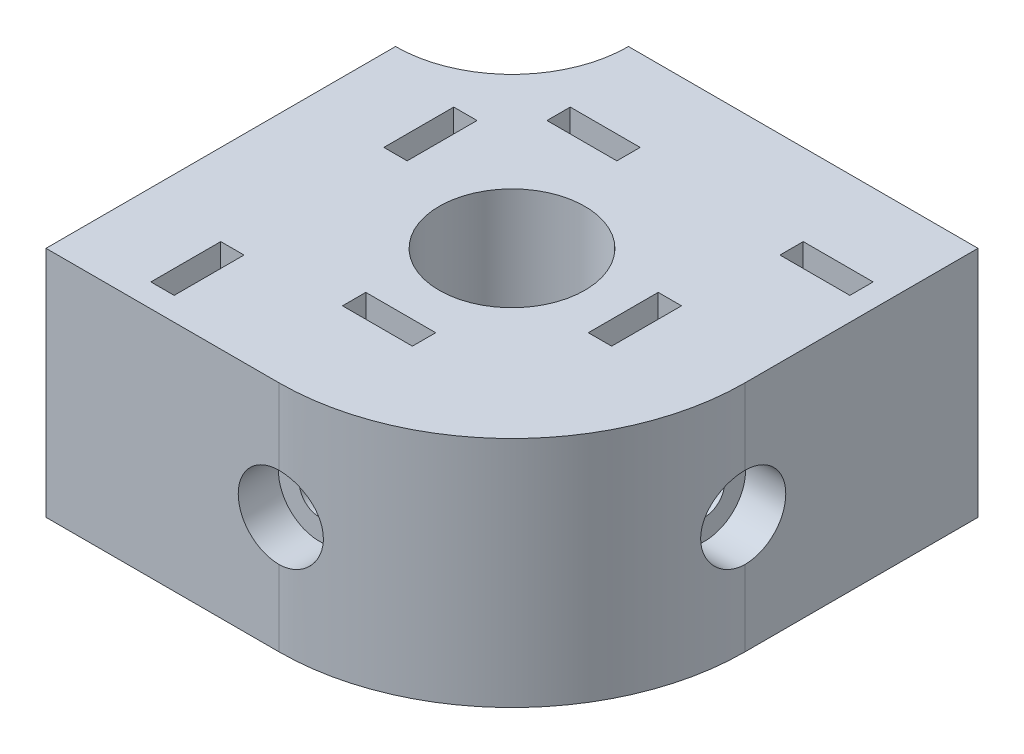
SolidWorks part; units mm, degrees
ref_plane "Front Plane" through (0, 0, 0) normal (0, 0, 1) x (1, 0, 0)
ref_plane "Top Plane" through (0, 0, 0) normal (0, 1, 0) x (1, 0, 0)
ref_plane "Right Plane" through (0, 0, 0) normal (1, 0, 0) x (0, 0, -1)
sketch "Sketch1" plane through (0, 0, 0) normal (0, 1, 0) x (1, 0, 0)
  line L1 (-20, -20) -> (20, -20)
  line L2 (-20, -20) -> (-20, 20)
  line L3 (-20, 20) -> (20, 20)
  line L4 (20, -20) -> (20, 20)
  line L5 (-20, -20) -> (20, 20) construction
  line L6 (-20, 20) -> (20, -20) construction
  circle A0 centre (0, 0) radius 6.25
  point P0 (0, 0)
  dimension "D2" = 12.5
  dimension "D1" = 40
extrude "Boss-Extrude1" add sketch "Sketch1" along normal blind 20
sketch "Sketch2" plane through (-20, 0, 0) normal (-1, 0, 0) x (0, 0, 1)
  line L0 (-5, 15) -> (0, 5) construction
  line L1 (0, 5) -> (15, 15) construction
  line L2 (15, 15) -> (-5, 15) construction
  line L3 (-20, 20) -> (20, 20) construction
  line L4 (-20, 0) -> (20, 0) construction
  line L5 (20, 20) -> (20, 0) construction
  line L6 (-20, 20) -> (-20, 0) construction
  line L7 (0, -11) -> (0, 11) construction
  circle A0 centre (-5, 15) radius 1.7
  circle A1 centre (15, 15) radius 1.7
  circle A2 centre (0, 5) radius 1.7
  dimension "D5" = 3.4
  dimension "D1" = 5
  dimension "D2" = 5
  dimension "D3" = 5
  dimension "D4" = 15
extrude "Cut-Extrude1" cut sketch "Sketch2" against normal blind 11
sketch "Sketch3" plane through (-20, 0, 0) normal (-1, 0, 0) x (0, 0, 1)
  line L1 (-8, 12) -> (-2, 12)
  line L2 (-8, 12) -> (-8, 18)
  line L3 (-8, 18) -> (-2, 18) construction
  line L4 (-2, 12) -> (-2, 18)
  line L5 (-8, 12) -> (-2, 18) construction
  line L6 (-8, 18) -> (-2, 12) construction
  line L7 (12, 12) -> (18, 12)
  line L8 (12, 12) -> (12, 18)
  line L9 (12, 18) -> (18, 18) construction
  line L10 (18, 12) -> (18, 18)
  line L11 (12, 12) -> (18, 18) construction
  line L12 (12, 18) -> (18, 12) construction
  line L13 (-3, 8) -> (3, 8)
  line L14 (-3, 8) -> (-3, 2)
  line L15 (-3, 2) -> (3, 2) construction
  line L16 (3, 8) -> (3, 2)
  line L17 (-3, 8) -> (3, 2) construction
  line L18 (-3, 2) -> (3, 8) construction
  line L20 (-8, 18) -> (-8, 20)
  line L21 (-20, 20) -> (20, 20) construction
  line L22 (-8, 20) -> (-2, 20)
  line L23 (-2, 20) -> (-2, 18)
  line L24 (12, 18) -> (12, 20)
  line L25 (12, 20) -> (18, 20)
  line L26 (18, 20) -> (18, 18)
  line L27 (-3, 2) -> (-3, 0)
  line L28 (-20, 0) -> (20, 0) construction
  line L29 (-3, 0) -> (3, 0)
  line L30 (3, 0) -> (3, 2)
  point P0 (-5, 15)
  point P6 (15, 15)
  point P12 (0, 5)
  dimension "D1" = 6
  dimension "D2" = 6
extrude "Cut-Extrude2" cut sketch "Sketch3" against normal blind 2 from offset 7 offset against normal yes
sketch "Sketch4" plane through (0, 0, 20) normal (0, 0, 1) x (1, 0, 0)
  line L0 (0, 0) -> (0, 20) construction
  line L1 (-20, 20) -> (20, 20) construction
  circle A0 centre (0, 10) radius 1.7
  dimension "D1" = 3.4
extrude "Cut-Extrude3" cut sketch "Sketch4" against normal up to next
sketch "Sketch5" plane through (0, 0, 20) normal (0, 0, 1) x (1, 0, 0)
  line L0 (-3, 13) -> (-3, 20)
  line L1 (-3, 7) -> (3, 7)
  line L2 (-3, 7) -> (-3, 13)
  line L3 (-3, 13) -> (3, 13) construction
  line L4 (3, 7) -> (3, 13)
  line L5 (-3, 7) -> (3, 13) construction
  line L6 (-3, 13) -> (3, 7) construction
  line L7 (-20, 20) -> (20, 20) construction
  line L8 (-3, 20) -> (3, 20)
  line L9 (3, 20) -> (3, 13)
  point P0 (0, 10)
  dimension "D1" = 6
extrude "Cut-Extrude4" cut sketch "Sketch5" against normal blind 2 from offset 8.45 offset against normal yes
sketch "Sketch6" plane through (0, 0, 20) normal (0, 0, 1) x (1, 0, 0)
  circle A0 centre (0, 10) radius 3.5
  dimension "D1" = 7
extrude "Cut-Extrude5" cut sketch "Sketch6" against normal blind 3.45
ref_plane "Plane1" through (0, 0, 0) normal (-0.7071, 0, 0.7071) x (0.7071, 0, 0.7071)
mirror "Mirror1" about plane through (0, 0, 0) normal (-0.7071, 0, 0.7071) of "Cut-Extrude5", "Cut-Extrude4", "Cut-Extrude3", "Cut-Extrude2", "Cut-Extrude1"
fillet "Fillet1" radius 20 1 edges at (20, 10, 20)
sketch "Sketch7" plane through (0, 20, 0) normal (0, 1, 0) x (1, 0, 0)
  line L0 (20, 20) -> (-20, 20) construction
  line L1 (-20, 20) -> (-20, -20) construction
  line L2 (-20, 10) -> (-20, 20)
  line L3 (-20, 20) -> (-10, 20)
  arc A0 (-10, 20) -> (-20, 10) centre (-20, 20) cw
  dimension "D1" = 10
extrude "Cut-Extrude6" cut sketch "Sketch7" against normal through all
equation "\"M3_d\"= 3.4"
equation "\"D5@Sketch2\"= \"M3_d\""
equation "\"M3_nut_s\"= 6"
equation "\"M3_nut_m\"= 2"
equation "\"D1@Sketch3\"=\"M3_nut_s\""
equation "\"D2@Sketch3\"=\"M3_nut_s\" "
equation "\"D1@Cut-Extrude2\"=\"M3_nut_m\""
equation "\"D1@Sketch4\"=\"M3_d\""
equation "\"D1@Sketch5\"=\"M3_nut_s\""
equation "\"D1@Cut-Extrude4\"=\"M3_nut_m\""
